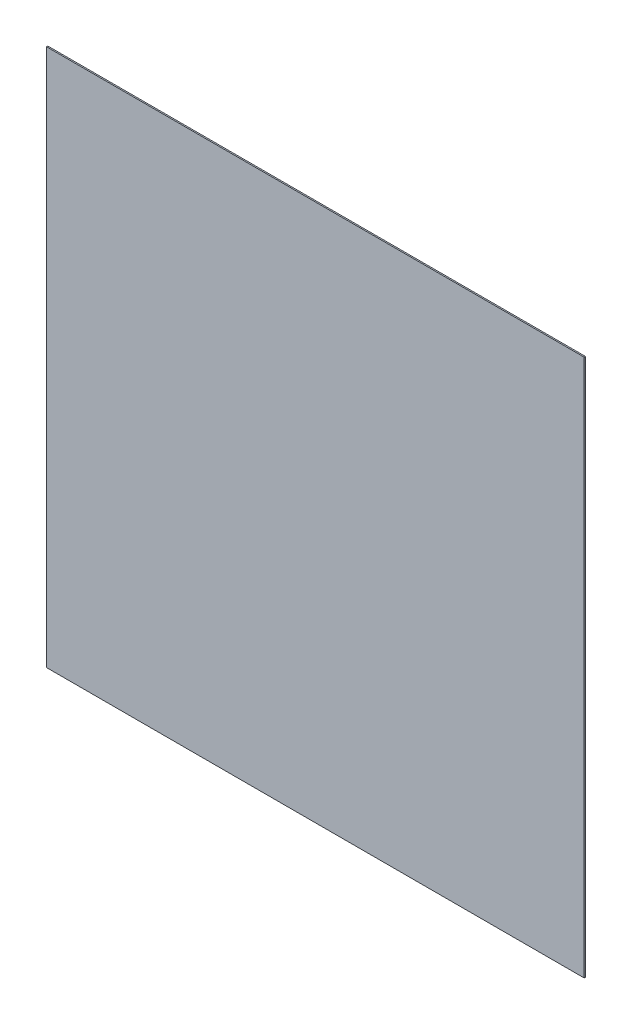
SolidWorks part; units mm, degrees
ref_plane "Front" through (0, 0, 0) normal (0, 0, 1) x (1, 0, 0)
ref_plane "Top" through (0, 0, 0) normal (0, 1, 0) x (1, 0, 0)
ref_plane "Right" through (0, 0, 0) normal (1, 0, 0) x (0, 0, -1)
sketch "Sketch1" plane through (0, 0, 0) normal (0, 0, 1) x (1, 0, 0)
  line L1 (-312.5, 312.5) -> (312.5, 312.5)
  line L2 (-312.5, 312.5) -> (-312.5, -312.5)
  line L3 (-312.5, -312.5) -> (312.5, -312.5)
  line L4 (312.5, 312.5) -> (312.5, -312.5)
  line L5 (-312.5, 312.5) -> (312.5, -312.5) construction
  line L6 (-312.5, -312.5) -> (312.5, 312.5) construction
  point P0 (0, 0)
  dimension "D1" = 625
  dimension "D2" = 625
extrude "Boss-Extrude1" add sketch "Sketch1" along normal blind 1.5
sketch "Sketch2" plane through (0, 0, 0) normal (0, 0, -1) x (-1, 0, 0)
  line L0 (-312.5, 312.5) -> (312.5, 312.5) construction
  line L1 (312.5, 312.5) -> (312.5, -312.5) construction
  line L2 (-91.4177, 0) -> (78.2357, 0) construction
  line L3 (0, 61.169) -> (0, -78.8952) construction
  line L4 (-312.5, -312.5) -> (-312.5, 312.5) construction
  circle A0 centre (0, 292.5) radius 5
  circle A1 centre (-292.5, 0) radius 5
  circle A2 centre (0, -292.5) radius 5
  circle A3 centre (292.5, 0) radius 5
  dimension "D1" = 10
  dimension "D4" = 10
  dimension "D2" = 20
  dimension "D3" = 312.5
  dimension "D5" = 20
  dimension "D6" = 312.5
extrude "Boss-Extrude2" add sketch "Sketch2" along normal blind 1.5
